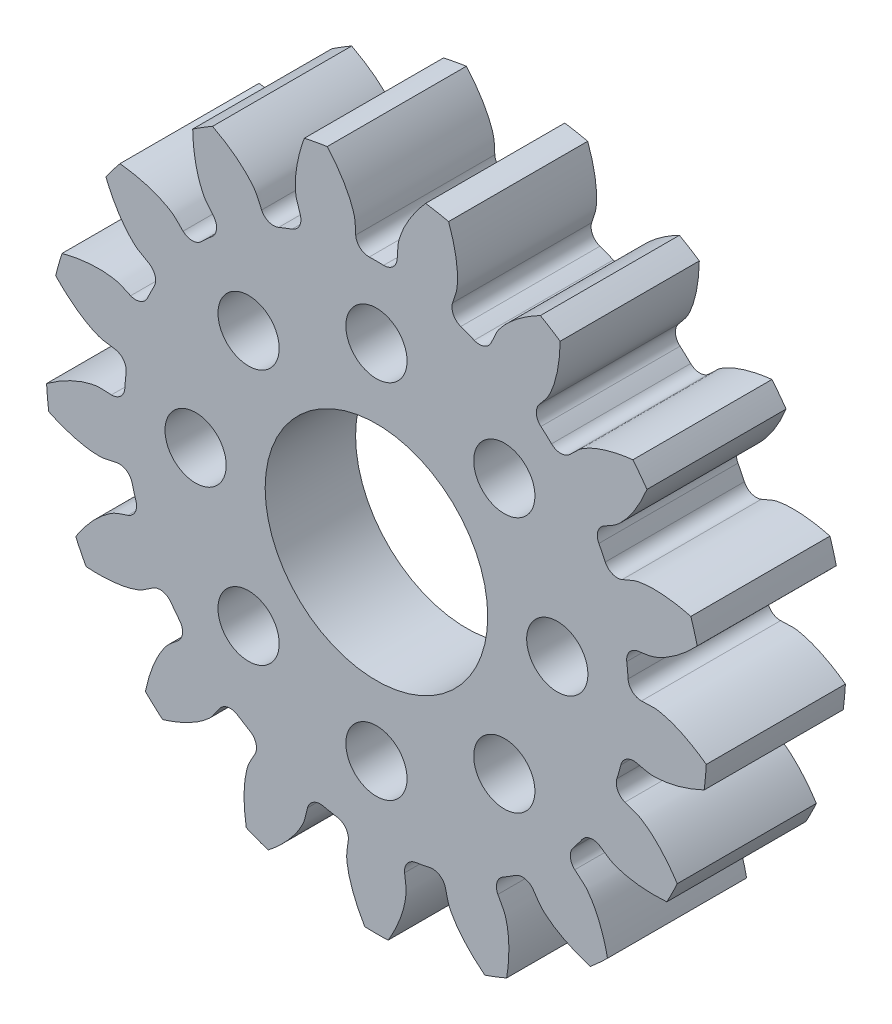
SolidWorks part; units mm, degrees
material "POM 乙缩醛共聚物"
ref_plane "前视基准面" through (0, 0, 0) normal (0, 0, 1) x (1, 0, 0)
ref_plane "上视基准面" through (0, 0, 0) normal (0, 1, 0) x (1, 0, 0)
ref_plane "右视基准面" through (0, 0, 0) normal (1, 0, 0) x (0, 0, -1)
ref_axis "Axis1" through (0, 0, -88.99) along (0, 0, 1)
sketch "草图1" plane through (0, 0, 0) normal (0, 0, 1) x (1, 0, 0)
  circle A0 centre (0, 0) radius 9.5
extrude "LaShenA" add sketch "草图1" along normal blind 4
sketch "SketchA" plane through (0, 0, 4) normal (0, 0, 1) x (1, 0, 0)
  line L0 (0, 0) -> (0, 9.5) construction
  arc A0 (0.207, 7.247) -> (-0.207, 7.247) centre (0, 0) ccw
  arc A1 (1.9284, 9.9057) -> (-1.9284, 9.9057) centre (0, 0) ccw
  arc A2 (-0.207, 7.247) -> (-0.5968, 7.5982) centre (-0.2179, 7.6269) cw
  arc A3 (0.5968, 7.5982) -> (0.207, 7.247) centre (0.2179, 7.6269) cw
  circle A4 centre (0, 0) radius 7.9874 construction
  circle A5 centre (0, 0) radius 9.5 construction
  circle A6 centre (0, 0) radius 7.25 construction
  circle A7 centre (0, 0) radius 8.5 construction
  spline S0 degree 3 poles (0.5968, 7.5982) (0.606, 7.7206) (0.6026, 7.8698) (0.6296, 8.029) (0.6422, 8.0808) (0.6533, 8.1218) (0.6675, 8.1687) (0.685, 8.2214) (0.7063, 8.2797) (0.7317, 8.3435) (0.7614, 8.4125) (0.7959, 8.4865) (0.8354, 8.5654) (0.8802, 8.6489) (0.9307, 8.7367) (0.987, 8.8286) (1.0495, 8.9244) (1.1185, 9.0236) (1.1941, 9.1262) (1.2767, 9.2316) (1.3664, 9.3397) (1.4635, 9.4501) (1.5682, 9.5624) (1.7212, 9.7175) (1.8433, 9.8309) (1.9284, 9.9057) knots 0.121184 0.121184 0.121184 0.121184 0.238206 0.264317 0.275812 0.289397 0.305072 0.322837 0.342692 0.364637 0.388672 0.414798 0.443013 0.473318 0.505713 0.540198 0.576773 0.615438 0.656194 0.699039 0.743974 0.790999 0.840114 0.89132 1 1 1 1
  spline S1 degree 3 poles (-0.5968, 7.5982) (-0.606, 7.7206) (-0.6026, 7.8698) (-0.6296, 8.029) (-0.6422, 8.0808) (-0.6533, 8.1218) (-0.6675, 8.1687) (-0.685, 8.2214) (-0.7063, 8.2797) (-0.7317, 8.3435) (-0.7614, 8.4125) (-0.7959, 8.4865) (-0.8354, 8.5654) (-0.8802, 8.6489) (-0.9307, 8.7367) (-0.987, 8.8286) (-1.0495, 8.9244) (-1.1185, 9.0236) (-1.1941, 9.1262) (-1.2767, 9.2316) (-1.3664, 9.3397) (-1.4635, 9.4501) (-1.5682, 9.5624) (-1.7212, 9.7175) (-1.8433, 9.8309) (-1.9284, 9.9057) knots 0.121184 0.121184 0.121184 0.121184 0.238206 0.264317 0.275812 0.289397 0.305072 0.322837 0.342692 0.364637 0.388672 0.414798 0.443013 0.473318 0.505713 0.540198 0.576773 0.615438 0.656194 0.699039 0.743974 0.790999 0.840114 0.89132 1 1 1 1
  dimension "D1" = 0.38
  dimension "Db" = 15.9748
  dimension "Da" = 19
  dimension "Df" = 14.5
  dimension "Dn" = 17
extrude "Cut-ExtrudeA" cut sketch "SketchA" against normal blind 30
pattern_circular "www.KYTool.cn" count 17 over 360 about axis through (0, 0, -88.99) along (0, 0, 1) of "Cut-ExtrudeA"
scale "缩放比例1" scale about centroid uniform scaling yes scale factor 1.25
sketch "草图3" plane through (0, 0, -0.5) normal (0, 0, -1) x (-1, 0, 0)
  circle A5 centre (0, 0) radius 9
  dimension "D1" = 18
extrude "切除-拉伸2" cut sketch "草图3" against normal blind 1.75
sketch "草图4" plane through (0, 0, 1.25) normal (0, 0, -1) x (-1, 0, 0)
  circle A2 centre (0, 0) radius 2.5
  dimension "D1" = 5
extrude "切除-拉伸3" cut sketch "草图4" against normal through all
sketch "草图5" plane through (0, 0, -0.5) normal (0, 0, -1) x (-1, 0, 0)
  circle A0 centre (0, 0) radius 4
  dimension "D1" = 8
extrude "切除-拉伸4" cut sketch "草图5" against normal through all
sketch "草图6" plane through (0, 0, 4.5) normal (0, 0, 1) x (1, 0, 0)
  circle A0 centre (0, 0) radius 10.63 construction
  dimension "D1" = 21.26
sketch "草图7" plane through (0, 0, 4.5) normal (0, 0, 1) x (1, 0, 0)
  circle A0 centre (0, 6.5) radius 1.1
  circle A1 centre (4.5962, 4.5962) radius 1.1
  circle A2 centre (6.5, 0) radius 1.1
  circle A3 centre (4.5962, -4.5962) radius 1.1
  circle A4 centre (0, -6.5) radius 1.1
  circle A5 centre (-4.5962, -4.5962) radius 1.1
  circle A6 centre (-6.5, 0) radius 1.1
  circle A7 centre (-4.5962, 4.5962) radius 1.1
  point P19 (0, 0)
  dimension "D1" = 2.2
  dimension "D2" = 8
  dimension "D3" = 13
extrude "切除-拉伸5" cut sketch "草图7" against normal through all
